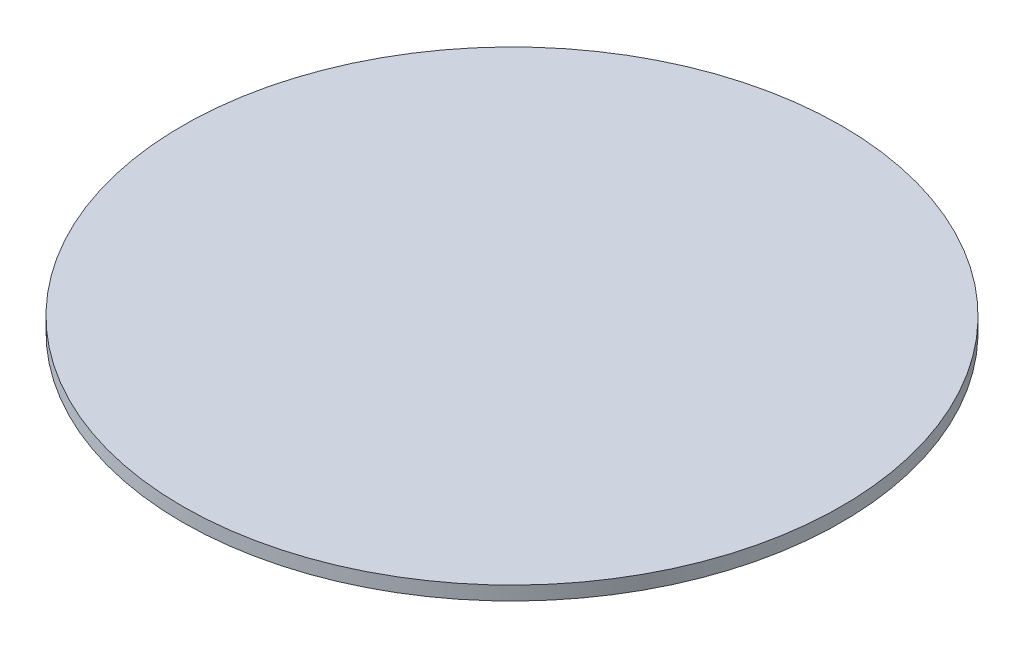
SolidWorks part; units mm, degrees
material "6061-T6 (SS)"
ref_plane "Front Plane" through (0, 0, 0) normal (0, 0, 1) x (1, 0, 0)
ref_plane "Top Plane" through (0, 0, 0) normal (0, 1, 0) x (1, 0, 0)
ref_plane "Right Plane" through (0, 0, 0) normal (1, 0, 0) x (0, 0, -1)
sketch "Sketch1" plane through (0, 0, 0) normal (0, 1, 0) x (1, 0, 0)
  circle A0 centre (0, 0) radius 2385
  dimension "D1" = 4770
extrude "Boss-Extrude1" add sketch "Sketch1" along normal blind 100 contours A0
